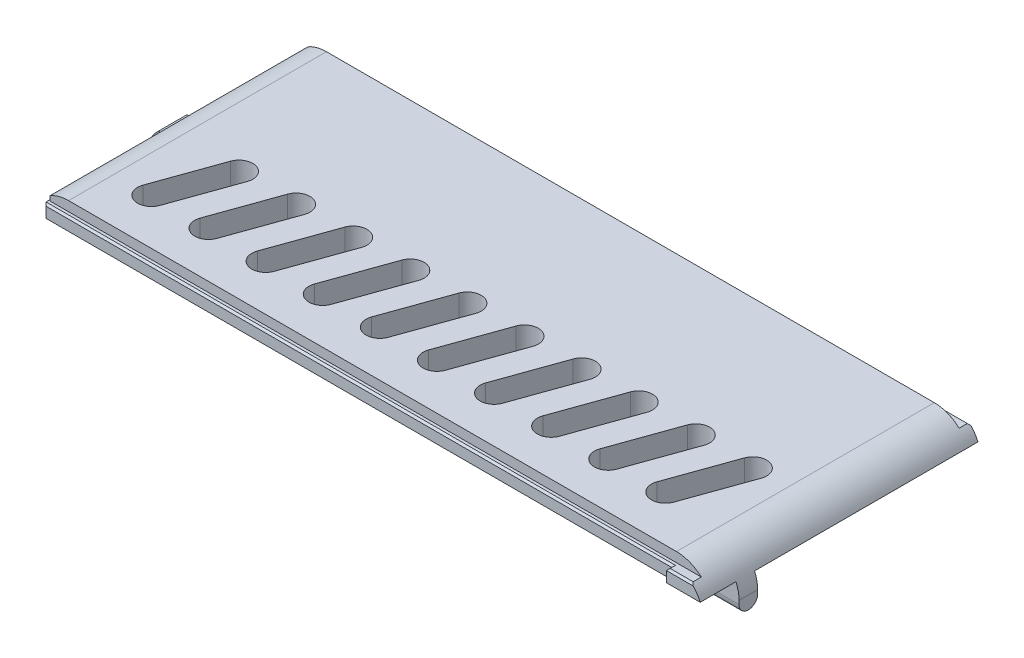
SolidWorks part; units mm, degrees
ref_plane "前视基准面" through (0, 0, 0) normal (0, 0, 1) x (1, 0, 0)
ref_plane "上视基准面" through (0, 0, 0) normal (0, 1, 0) x (1, 0, 0)
ref_plane "右视基准面" through (0, 0, 0) normal (1, 0, 0) x (0, 0, -1)
sketch "草图2" plane through (0, 0, 0) normal (0, 1, 0) x (1, 0, 0)
  line L1 (-31.0872, 15.1404) -> (42.9128, 15.1404)
  line L2 (-31.0872, 15.1404) -> (-31.0872, -12.8596)
  line L3 (-31.0872, -12.8596) -> (42.9128, -12.8596)
  line L4 (42.9128, 15.1404) -> (42.9128, -12.8596)
  dimension "D1" = 74
  dimension "D2" = 28
extrude "凸台-拉伸1" add sketch "草图2" along normal blind 4
fillet "圆角1" radius 4 2 edges at (-31.0872, 4, -1.1404) (42.9128, 4, -1.1404)
sketch "草图3" plane through (0, 0, -15.1404) normal (0, 0, -1) x (-1, 0, 0)
  line L1 (31.0872, 0) -> (-42.9128, 0)
  line L2 (31.0872, 0) -> (31.0872, 1.6)
  line L3 (31.0872, 1.6) -> (-42.9128, 1.6)
  line L4 (-42.9128, 0) -> (-42.9128, 1.6)
  line L5 (31.0872, 0) -> (31.0872, -28) construction
  dimension "D1" = 1.6
extrude "切除-拉伸1" cut sketch "草图3" against normal through all
sketch "草图15" plane through (0, 1.6, 0) normal (0, -1, 0) x (1, 0, 0)
  line L1 (45.2778, 8.0374) -> (33.5789, 8.0374)
  line L2 (45.2778, 8.0374) -> (45.2778, 10.0596)
  line L3 (45.2778, 10.0596) -> (33.5789, 10.0596)
  line L4 (33.5789, 8.0374) -> (33.5789, 10.0596)
  line L5 (42.5789, -15.1404) -> (42.5789, 12.8596) construction
  dimension "D1" = 2.0222
  dimension "D2" = 9
extrude "凸台-拉伸8" add sketch "草图15" along normal blind 3
sketch "草图17" plane through (0, 0, 10.0596) normal (0, 0, 1) x (1, 0, 0)
  line L0 (42.9128, 0) -> (42.9128, -28) construction
  line L1 (42.9128, 0) -> (42.9128, -1.4)
  line L2 (45.2778, -1.4) -> (33.5789, -1.4) construction
  line L3 (42.9128, -1.4) -> (46.903, -1.4)
  line L4 (46.903, -1.4) -> (46.903, 1.6)
  line L5 (46.903, 1.6) -> (42.5789, 1.6)
  arc A0 (42.5789, 1.6) -> (42.9128, 0) centre (38.9128, 0) cw
extrude "切除-拉伸5" cut sketch "草图17" against normal through all
chamfer "倒角3" distance 3.5 angle 19 1 edges at (33.5789, 0.1, 10.0596) first distance on face at (39.129, 0.0834, 10.0596)
sketch "草图4" plane through (0, 0, 12.8596) normal (0, 0, 1) x (1, 0, 0)
  line L0 (-31.0872, 0) -> (-31.0872, -28) construction
  line L1 (-31.0872, -1.1213) -> (-29.0872, -1.1213)
  line L2 (-31.0872, -1.1213) -> (-31.0872, 6.7558)
  line L3 (-31.0872, 6.7558) -> (-29.0872, 6.7558)
  line L4 (-29.0872, -1.1213) -> (-29.0872, 6.7558)
  dimension "D1" = 2
extrude "切除-拉伸2" cut sketch "草图4" against normal through all
sketch "草图5" plane through (0, 0, 12.8596) normal (0, 0, 1) x (1, 0, 0)
  line L0 (-29.0872, 1.6) -> (42.5789, 1.6) construction
  line L1 (38.9128, 1.6) -> (-29.0872, 1.6)
  line L2 (38.9128, 1.6) -> (38.9128, 2.95)
  line L3 (38.9128, 2.95) -> (-29.0872, 2.95)
  line L4 (-29.0872, 1.6) -> (-29.0872, 2.95)
  line L6 (-29.0872, 1.6) -> (-29.0872, 3.4641) construction
  dimension "D1" = 1.35
extrude "凸台-拉伸2" add sketch "草图5" along normal blind 0.5
sketch "草图6" plane through (0, 0, -15.1404) normal (0, 0, -1) x (-1, 0, 0)
  line L4 (-38.9128, 2.95) -> (-38.9128, 1.6)
  line L5 (29.0872, 2.95) -> (-38.9128, 2.95)
  line L6 (29.0872, 1.6) -> (29.0872, 2.95)
  line L7 (-38.9128, 1.6) -> (29.0872, 1.6)
  line L8 (-38.9128, 2.95) -> (-38.9128, 1.6)
  line L9 (29.0872, 2.95) -> (-38.9128, 2.95)
  line L10 (29.0872, 1.6) -> (29.0872, 2.95)
  line L11 (-38.9128, 1.6) -> (29.0872, 1.6)
  dimension "D1" = 0
extrude "凸台-拉伸3" add sketch "草图6" along normal blind 0.5
sketch "草图7" plane through (-29.0872, 0, 0) normal (-1, 0, 0) x (0, 0, 1)
  line L1 (13.3596, 2.95) -> (-15.6404, 2.95)
  line L2 (13.3596, 2.95) -> (13.3596, 1.6)
  line L3 (13.3596, 1.6) -> (-15.6404, 1.6)
  line L4 (-15.6404, 2.95) -> (-15.6404, 1.6)
extrude "凸台-拉伸4" add sketch "草图7" along normal blind 0.15
sketch "草图10" plane through (0, 0, -15.1404) normal (0, 0, -1) x (-1, 0, 0)
  line L0 (-38.9128, 2.95) -> (-42.3685, 2.95) construction
  line L1 (-42.5789, 1.6) -> (-38.9128, 1.6)
  line L2 (-38.9128, 1.6) -> (-38.9128, 2.95)
  line L3 (-38.9128, 2.95) -> (-41.6142, 2.95)
  arc A0 (-42.5789, 1.6) -> (-41.6142, 2.95) centre (-38.9128, 0) cw
extrude "凸台-拉伸5" add sketch "草图10" along normal blind 1.08
sketch "草图11" plane through (0, 0, 12.8596) normal (0, 0, 1) x (1, 0, 0)
  line L3 (38.9128, 1.6) -> (42.5789, 1.6)
  line L4 (38.9128, 2.95) -> (38.9128, 1.6)
  line L5 (41.6142, 2.95) -> (38.9128, 2.95)
  line L6 (38.9128, 1.6) -> (42.5789, 1.6)
  line L7 (38.9128, 2.95) -> (38.9128, 1.6)
  line L8 (41.6142, 2.95) -> (38.9128, 2.95)
  arc A1 (42.5789, 1.6) -> (41.6142, 2.95) centre (38.9128, 0) ccw
  arc A2 (42.5789, 1.6) -> (41.6142, 2.95) centre (38.9128, 0) ccw
  dimension "D1" = 0
extrude "凸台-拉伸6" add sketch "草图11" along normal blind 1.08
chamfer "倒角1" distance 0.2 angle 45 9 edges at (40.2635, 2.95, -16.2204) (40.2635, 2.95, 13.9396) (4.8378, 2.95, -15.6404) (-29.2372, 2.275, -15.6404) (-29.2372, 1.6, -1.1404) (-29.2372, 2.275, 13.3596) (4.8378, 2.95, 13.3596) (38.9128, 2.95, -15.9304) (38.9128, 2.95, 13.6496)
sketch "草图12" plane through (-29.2372, 0, 0) normal (-1, 0, 0) x (0, 0, 1)
  line L0 (-1.1404, 1.8) -> (-1.1404, 4.7248) construction
  line L2 (-15.4404, 1.8) -> (13.1596, 1.8) construction
  line L3 (14.3032, 2.375) -> (12.788, 2.375) construction
  line L4 (13.1596, 1.8) -> (13.1596, 2.95) construction
  line L6 (0.4096, 2.95) -> (-2.6904, 2.95)
  line L7 (0.4096, 2.95) -> (0.4096, 1.8)
  line L8 (0.4096, 1.8) -> (-2.6904, 1.8)
  line L9 (-2.6904, 2.95) -> (-2.6904, 1.8)
  line L10 (0.4096, 2.95) -> (-2.6904, 1.8) construction
  line L11 (0.4096, 1.8) -> (-2.6904, 2.95) construction
  point P3 (-1.1404, 1.8)
  point P6 (-1.1404, 2.375)
  point P9 (13.1596, 2.375)
  dimension "D1" = 3.1
extrude "凸台-拉伸7" add sketch "草图12" along normal blind 10
sketch "草图14" plane through (0, 0, -2.6904) normal (0, 0, -1) x (-1, 0, 0)
  line L0 (39.2372, 1.8) -> (29.2372, 1.8) construction
  line L1 (39.2372, 2.95) -> (29.2372, 2.95) construction
  line L2 (29.7886, 2.95) -> (40.0135, 2.95)
  line L3 (40.0135, 2.95) -> (40.0135, 1.8)
  line L4 (40.0135, 1.8) -> (30.6593, 1.8)
  arc A0 (30.6593, 1.8) -> (29.7886, 2.95) centre (27.0872, 0) ccw
  arc A1 (31.0872, 0) -> (27.0872, 4) centre (27.0872, 0) ccw construction
extrude "切除-拉伸3" cut sketch "草图14" against normal through all
fillet "圆角2" radius 1 2 edges at (38.2459, -1.4, 8.0374) (39.9959, -1.4, 10.0596)
sketch "草图19" plane through (0, 4, 0) normal (0, 1, 0) x (1, 0, 0)
  line L0 (-20.5872, -0.8596) -> (-23.0872, -7.8596) construction
  line L5 (-19.1746, -1.3641) -> (-21.6746, -8.3641)
  line L8 (-21.9998, -0.3551) -> (-24.4998, -7.3551)
  line L11 (38.9128, 15.1404) -> (-27.0872, 15.1404) construction
  line L14 (-27.0872, -12.8596) -> (38.9128, -12.8596) construction
  line L17 (-14.3872, -0.8596) -> (-16.8872, -7.8596) construction
  line L20 (-12.9746, -1.3641) -> (-15.4746, -8.3641)
  line L23 (-15.7998, -0.3551) -> (-18.2998, -7.3551)
  line L26 (-40.9597, 1.1404) -> (-18.0872, 1.1404) construction
  line L27 (-27.0872, 15.1404) -> (-27.0872, -12.8596) construction
  line L28 (-8.1872, -0.8596) -> (-10.6872, -7.8596) construction
  line L31 (-6.7746, -1.3641) -> (-9.2746, -8.3641)
  line L34 (-9.5998, -0.3551) -> (-12.0998, -7.3551)
  line L37 (-1.9872, -0.8596) -> (-4.4872, -7.8596) construction
  line L40 (-0.5746, -1.3641) -> (-3.0746, -8.3641)
  line L43 (-3.3998, -0.3551) -> (-5.8998, -7.3551)
  line L46 (4.2128, -0.8596) -> (1.7128, -7.8596) construction
  line L49 (5.6254, -1.3641) -> (3.1254, -8.3641)
  line L52 (2.8002, -0.3551) -> (0.3002, -7.3551)
  line L53 (10.4128, -0.8596) -> (7.9128, -7.8596) construction
  line L54 (11.8254, -1.3641) -> (9.3254, -8.3641)
  line L55 (9.0002, -0.3551) -> (6.5002, -7.3551)
  line L56 (16.6128, -0.8596) -> (14.1128, -7.8596) construction
  line L57 (18.0254, -1.3641) -> (15.5254, -8.3641)
  line L58 (15.2002, -0.3551) -> (12.7002, -7.3551)
  line L59 (22.8128, -0.8596) -> (20.3128, -7.8596) construction
  line L60 (24.2254, -1.3641) -> (21.7254, -8.3641)
  line L61 (21.4002, -0.3551) -> (18.9002, -7.3551)
  line L62 (29.0128, -0.8596) -> (26.5128, -7.8596) construction
  line L63 (30.4254, -1.3641) -> (27.9254, -8.3641)
  line L64 (27.6002, -0.3551) -> (25.1002, -7.3551)
  line L65 (35.2128, -0.8596) -> (32.7128, -7.8596) construction
  line L66 (36.6254, -1.3641) -> (34.1254, -8.3641)
  line L67 (33.8002, -0.3551) -> (31.3002, -7.3551)
  arc A32 (-19.1746, -1.3641) -> (-21.9998, -0.3551) centre (-20.5872, -0.8596) ccw
  arc A33 (-24.4998, -7.3551) -> (-21.6746, -8.3641) centre (-23.0872, -7.8596) ccw
  arc A34 (-12.9746, -1.3641) -> (-15.7998, -0.3551) centre (-14.3872, -0.8596) ccw
  arc A35 (-18.2998, -7.3551) -> (-15.4746, -8.3641) centre (-16.8872, -7.8596) ccw
  arc A36 (-6.7746, -1.3641) -> (-9.5998, -0.3551) centre (-8.1872, -0.8596) ccw
  arc A37 (-12.0998, -7.3551) -> (-9.2746, -8.3641) centre (-10.6872, -7.8596) ccw
  arc A38 (-0.5746, -1.3641) -> (-3.3998, -0.3551) centre (-1.9872, -0.8596) ccw
  arc A39 (-5.8998, -7.3551) -> (-3.0746, -8.3641) centre (-4.4872, -7.8596) ccw
  arc A40 (5.6254, -1.3641) -> (2.8002, -0.3551) centre (4.2128, -0.8596) ccw
  arc A41 (0.3002, -7.3551) -> (3.1254, -8.3641) centre (1.7128, -7.8596) ccw
  arc A42 (11.8254, -1.3641) -> (9.0002, -0.3551) centre (10.4128, -0.8596) ccw
  arc A43 (6.5002, -7.3551) -> (9.3254, -8.3641) centre (7.9128, -7.8596) ccw
  arc A44 (18.0254, -1.3641) -> (15.2002, -0.3551) centre (16.6128, -0.8596) ccw
  arc A45 (12.7002, -7.3551) -> (15.5254, -8.3641) centre (14.1128, -7.8596) ccw
  arc A46 (24.2254, -1.3641) -> (21.4002, -0.3551) centre (22.8128, -0.8596) ccw
  arc A47 (18.9002, -7.3551) -> (21.7254, -8.3641) centre (20.3128, -7.8596) ccw
  arc A48 (30.4254, -1.3641) -> (27.6002, -0.3551) centre (29.0128, -0.8596) ccw
  arc A49 (25.1002, -7.3551) -> (27.9254, -8.3641) centre (26.5128, -7.8596) ccw
  arc A50 (36.6254, -1.3641) -> (33.8002, -0.3551) centre (35.2128, -0.8596) ccw
  arc A51 (31.3002, -7.3551) -> (34.1254, -8.3641) centre (32.7128, -7.8596) ccw
  point P2 (-21.8372, -4.3596)
  point P15 (-15.6372, -4.3596)
  point P22 (-9.4372, -4.3596)
  point P29 (-3.2372, -4.3596)
  point P36 (2.9628, -4.3596)
  point P43 (9.1628, -4.3596)
  point P50 (15.3628, -4.3596)
  point P57 (21.5628, -4.3596)
  point P64 (-27.0872, 1.1404)
  point P68 (27.7628, -4.3596)
  point P75 (33.9628, -4.3596)
  dimension "D6" = 4
  dimension "D3" = 1.5
  dimension "D1" = 16
  dimension "D2" = 5
  dimension "D4" = 6.5
  dimension "D5" = 10
extrude "切除-拉伸6" cut sketch "草图19" against normal up to next
